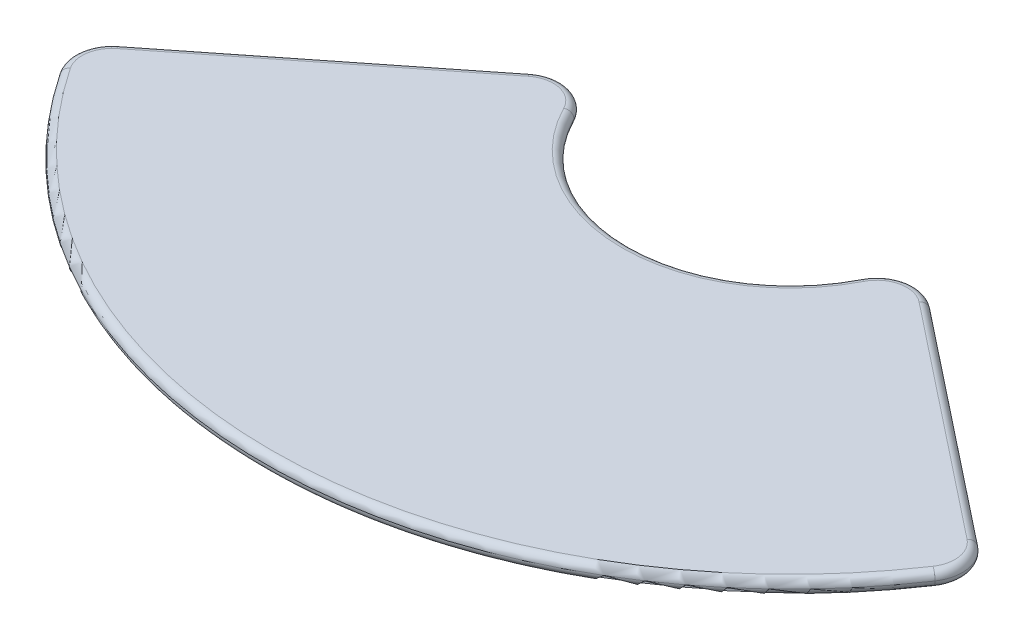
SolidWorks part; units mm, degrees
ref_plane "Front Plane" through (0, 0, 0) normal (0, 0, 1) x (1, 0, 0)
ref_plane "Top Plane" through (0, 0, 0) normal (0, 1, 0) x (1, 0, 0)
ref_plane "Right Plane" through (0, 0, 0) normal (1, 0, 0) x (0, 0, -1)
ref_plane "Plane9" through (0, 52, 0) normal (0, 1, 0) x (1, 0, 0)
sketch "Sketch19" plane through (0, 52, 0) normal (0, 1, 0) x (1, 0, 0)
  line L0 (-53.1766, 91.8773) -> (-114.1695, 43.6357)
  line L1 (0, 65.2967) -> (0, -31.8621) construction
  line L2 (53.1766, 91.8773) -> (114.1695, 43.6357)
  arc A0 (38.0698, 88.5871) -> (-38.0698, 88.5871) centre (0, 108.0557) cw
  arc A1 (116.2763, 30.2302) -> (-116.2763, 30.2302) centre (0, 108.0557) cw
  arc A2 (-38.0698, 88.5871) -> (-53.1766, 91.8773) centre (-46.9731, 84.034) ccw
  arc A3 (53.1766, 91.8773) -> (38.0698, 88.5871) centre (46.9731, 84.034) ccw
  arc A4 (116.2763, 30.2302) -> (114.1695, 43.6357) centre (107.966, 35.7924) ccw
  arc A5 (-116.2763, 30.2302) -> (-114.1695, 43.6357) centre (-107.966, 35.7924) cw
  point P7 (-42.1094, 100.6307)
  point P11 (42.1094, 100.6307)
  point P14 (121.1724, 38.0968)
  point P17 (-121.1724, 38.0968)
  dimension "D1" = 10
  dimension "D2" = 10
  dimension "D3" = 10
  dimension "D4" = 10
extrude "Boss-Extrude1" add sketch "Sketch19" along normal blind 4
fillet "Fillet1" radius 2 16 edges at (-83.6731, 52, -67.7565) (-117.8447, 52, -37.345) (0, 52, 31.8621) (117.8447, 52, -37.345) (83.6731, 52, -67.7565) (44.8451, 52, -93.805) (0, 52, -65.2967) (-44.8451, 52, -93.805) (0, 56, -65.2967) (44.8451, 56, -93.805) (83.6731, 56, -67.7565) (117.8447, 56, -37.345) (0, 56, 31.8621) (-117.8447, 56, -37.345) (-83.6731, 56, -67.7565) (-44.8451, 56, -93.805)
ref_axis "Axis1" through (-44.8451, 54, -93.805) along (1, 0, 0)
ref_plane "Plane10" through (0, 54, 0) normal (0, -1, 0) x (-1, 0, 0)
ref_plane "Plane11" through (0, 54, -65.2967) normal (1, 0, 0) x (0, 0, -1)
ref_plane "Plane12" through (117.8447, 0, 0) normal (1, 0, 0) x (0, 0, -1)
ref_plane "Plane13" through (-117.8447, 0, 0) normal (1, 0, 0) x (0, 0, -1)
ref_plane "Plane14" through (0, 0, 31.8621) normal (0, 0, 1) x (1, 0, 0)
ref_plane "Plane15" through (0, 0, -93.805) normal (0, 0, 1) x (1, 0, 0)
